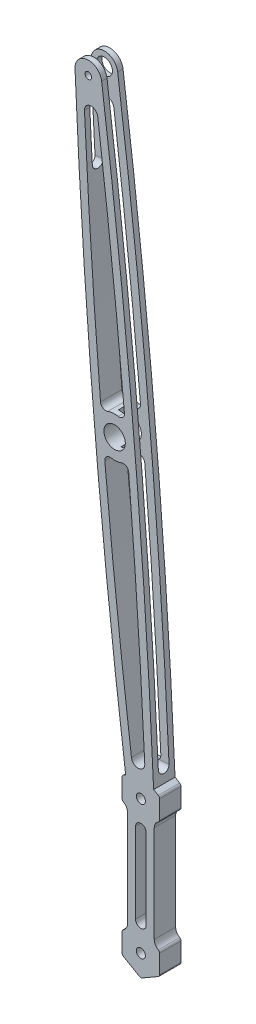
SolidWorks part; units mm, degrees
material "A2017"
ref_plane "正面" through (0, 0, 0) normal (0, 0, 1) x (1, 0, 0)
ref_plane "平面" through (0, 0, 0) normal (0, 1, 0) x (1, 0, 0)
ref_plane "右側面" through (0, 0, 0) normal (1, 0, 0) x (0, 0, -1)
sketch "ｽｹｯﾁ1" plane through (0, 0, 0) normal (0, 0, 1) x (1, 0, 0)
  line L0 (0, 0) -> (9.0749, 0) construction
  line L1 (0, 25) -> (0, 0) construction
  line L2 (0, -16.9171) -> (7, -20.9585)
  line L3 (7, 20.9585) -> (7, 29.0415)
  line L4 (7, 29.0415) -> (0, 33.0829)
  line L5 (0, 33.0829) -> (-7, 29.0415)
  line L6 (-7, 29.0415) -> (-7, 20.9585)
  line L7 (-7, 20.9585) -> (0, 16.9171)
  line L8 (0, 16.9171) -> (7, 20.9585)
  line L9 (-7, -20.9585) -> (0, -16.9171)
  line L10 (-7, -29.0415) -> (-7, -20.9585)
  line L11 (0, -33.0829) -> (-7, -29.0415)
  line L12 (7, -29.0415) -> (0, -33.0829)
  line L13 (7, -20.9585) -> (7, -29.0415)
  circle A0 centre (0, 25) radius 3
  circle A1 centre (0, -25) radius 3
  circle A2 centre (0, 25) radius 7 construction
  circle A3 centre (0, -25) radius 7 construction
  dimension "D1" = 6
  dimension "D2" = 50
  dimension "D3" = 14
extrude "ﾎﾞｽ - 押し出し1" add sketch "ｽｹｯﾁ1" along normal mid plane 8
sketch "ｽｹｯﾁ2" plane through (0, 0, 4) normal (0, 0, 1) x (1, 0, 0)
  line L0 (-7, 20.9585) -> (0, 16.9171) construction
  line L1 (5, -19.8038) -> (-5, -19.8038)
  line L2 (5, -19.8038) -> (5, 19.8038)
  line L3 (5, 19.8038) -> (-5, 19.8038)
  line L4 (-5, -19.8038) -> (-5, 19.8038)
  line L5 (5, -19.8038) -> (-5, 19.8038) construction
  line L6 (5, 19.8038) -> (-5, -19.8038) construction
  point P0 (0, 0)
  dimension "D1" = 10
extrude "ﾎﾞｽ - 押し出し2" add sketch "ｽｹｯﾁ2" against normal up to surface (8 mm away) up to face at (0, 25, -4)
fillet "ﾌｨﾚｯﾄ1" radius 3 4 edges at (5, -19.8038, 0) (-5, 19.8038, 0) (-5, -19.8038, 0) (5, 19.8038, 0)
fillet "ﾌｨﾚｯﾄ2" radius 1 10 edges at (-7, 20.9585, 0) (-7, 29.0415, 0) (0, 33.0829, 0) (7, 29.0415, 0) (7, 20.9585, 0) (7, -29.0415, 0) (0, -33.0829, 0) (-7, -29.0415, 0) (-7, -20.9585, 0) (7, -20.9585, 0)
sketch "ｽｹｯﾁ3" plane through (0, 0, -4) normal (0, 0, -1) x (-1, 0, 0)
  line L0 (0, -15) -> (0, 15) construction
  line L1 (-2, -15) -> (-2, 15)
  line L2 (2, -15) -> (2, 15)
  arc A0 (-2, -15) -> (2, -15) centre (0, -15) ccw
  arc A1 (2, 15) -> (-2, 15) centre (0, 15) ccw
  point P2 (0, 0)
  dimension "D1" = 4
  dimension "D2" = 30
extrude "ｶｯﾄ - 押し出し1" cut sketch "ｽｹｯﾁ3" against normal up to surface (8 mm away) up to face at (0, 0, 4)
sketch "ｽｹｯﾁ5" plane through (0, 0, 4) normal (0, 0, 1) x (1, 0, 0)
  circle A0 centre (0, -25) radius 3 construction
  circle A1 centre (0, 25) radius 3 construction
  circle A2 centre (0, -25) radius 3
  circle A3 centre (0, 25) radius 3
extrude "ﾎﾞｽ - 押し出し3" add sketch "ｽｹｯﾁ5" against normal blind 5
sketch "ｽｹｯﾁ8" [suppressed] plane through (0, 0, -4) normal (0, 0, -1) x (-1, 0, 0)
  circle A0 centre (0, -25) radius 3 construction
  circle A1 centre (0, 25) radius 3 construction
  circle A2 centre (0, -25) radius 3
  circle A3 centre (0, 25) radius 3
extrude "ﾎﾞｽ - 押し出し4" [suppressed] add sketch "ｽｹｯﾁ8" against normal blind 5
hole_wizard "M3 すきま穴1" positions "ｽｹｯﾁ6" profile "ｽｹｯﾁ7" hole size "M3" standard "JIS" end condition through all
sketch "ｽｹｯﾁ6" plane through (0, 0, 4) normal (0, 0, -1) x (-1, 0, 0)
  point P0 (0, 25)
  point P3 (0, -25)
sketch "ｽｹｯﾁ7" plane through (0, 25, 4) normal (1, 0, 0) x (0, -1, 0)
  line L0 (0, 0) -> (0, 8)
  line L1 (0, 8) -> (1.7, 8)
  line L2 (1.7, 8) -> (1.7, 0)
  line L5 (1.7, 0) -> (0, 0)
  line L11 (0, -6.35) -> (0, 107.95) construction
  dimension "通し穴の直径" = 3.4
  dimension "通し穴の深さ" = 8
sketch "ｽｹｯﾁ9" plane through (0, 0, 4) normal (0, 0, 1) x (1, 0, 0)
  line L0 (0, 25) -> (0, 298.9535) construction
  line L1 (0, 25) -> (-19.61, 249.1438) construction
  line L2 (0, 25) -> (-19.61, 249.1438) construction
  line L3 (-7.4715, 24.3463) -> (-27.0815, 248.4901) construction
  line L4 (7.4715, 25.6537) -> (-12.1386, 249.7975) construction
  line L15 (-7, 28.4641) -> (-7, 21.5359)
  line L16 (-5, 18.0718) -> (-5, -18.0718)
  line L17 (-7, -21.5359) -> (-7, -28.4641)
  line L18 (-6.5, -29.3301) -> (-0.5, -32.7942)
  line L19 (0.5, -32.7942) -> (6.5, -29.3301)
  line L20 (7, -28.4641) -> (7, -21.5359)
  line L21 (5, -18.0718) -> (5, 18.0718)
  line L22 (7, 21.5359) -> (7, 28.4641)
  line L23 (6.5, 29.3301) -> (0.5, 32.7942)
  line L24 (-0.5, 32.7942) -> (-6.5, 29.3301)
  line L25 (-7, 28.4641) -> (-7, 21.5359)
  line L26 (-5, 18.0718) -> (-5, -18.0718)
  line L27 (-7, -21.5359) -> (-7, -28.4641)
  line L28 (-6.5, -29.3301) -> (-0.5, -32.7942)
  line L29 (0.5, -32.7942) -> (6.5, -29.3301)
  line L30 (7, -28.4641) -> (7, -21.5359)
  line L31 (5, -18.0718) -> (5, 18.0718)
  line L32 (7, 21.5359) -> (7, 28.4641)
  line L33 (6.5, 29.3301) -> (0.5, 32.7942)
  line L34 (-0.5, 32.7942) -> (-6.5, 29.3301)
  arc A0 (-7.4715, 24.3463) -> (7.4715, 25.6537) centre (0, 25) ccw construction
  arc A1 (-12.1386, 249.7975) -> (-27.0815, 248.4901) centre (-19.61, 249.1438) ccw construction
  circle A2 centre (-19.61, 249.1438) radius 5 construction
  circle A3 centre (0, 25) radius 5
  arc A4 (-14.6533, 249.8004) -> (4.9954, 25.2141) centre (-2530.1776, -83.4321) cw
  arc A5 (-24.6055, 248.9297) -> (-4.9567, 24.3434) centre (2510.5676, 357.5759) ccw
  arc A6 (-14.6533, 249.8004) -> (-24.6055, 248.9297) centre (-19.61, 249.1438) ccw
  arc A16 (-7, 21.5359) -> (-6.5, 20.6699) centre (-6, 21.5359) ccw
  arc A17 (-5, 18.0718) -> (-6.5, 20.6699) centre (-8, 18.0718) ccw
  arc A18 (-6.5, -20.6699) -> (-5, -18.0718) centre (-8, -18.0718) ccw
  arc A19 (-6.5, -20.6699) -> (-7, -21.5359) centre (-6, -21.5359) ccw
  arc A20 (-7, -28.4641) -> (-6.5, -29.3301) centre (-6, -28.4641) ccw
  arc A21 (-0.5, -32.7942) -> (0.5, -32.7942) centre (0, -31.9282) ccw
  arc A22 (6.5, -29.3301) -> (7, -28.4641) centre (6, -28.4641) ccw
  arc A23 (7, -21.5359) -> (6.5, -20.6699) centre (6, -21.5359) ccw
  arc A24 (5, -18.0718) -> (6.5, -20.6699) centre (8, -18.0718) ccw
  arc A25 (6.5, 20.6699) -> (5, 18.0718) centre (8, 18.0718) ccw
  arc A26 (6.5, 20.6699) -> (7, 21.5359) centre (6, 21.5359) ccw
  arc A27 (7, 28.4641) -> (6.5, 29.3301) centre (6, 28.4641) ccw
  arc A28 (0.5, 32.7942) -> (-0.5, 32.7942) centre (0, 31.9282) ccw
  arc A29 (-6.5, 29.3301) -> (-7, 28.4641) centre (-6, 28.4641) ccw
  arc A30 (-7, 21.5359) -> (-6.5, 20.6699) centre (-6, 21.5359) ccw
  arc A31 (-5, 18.0718) -> (-6.5, 20.6699) centre (-8, 18.0718) ccw
  arc A32 (-6.5, -20.6699) -> (-5, -18.0718) centre (-8, -18.0718) ccw
  arc A33 (-6.5, -20.6699) -> (-7, -21.5359) centre (-6, -21.5359) ccw
  arc A34 (-7, -28.4641) -> (-6.5, -29.3301) centre (-6, -28.4641) ccw
  arc A35 (-0.5, -32.7942) -> (0.5, -32.7942) centre (0, -31.9282) ccw
  arc A36 (6.5, -29.3301) -> (7, -28.4641) centre (6, -28.4641) ccw
  arc A37 (7, -21.5359) -> (6.5, -20.6699) centre (6, -21.5359) ccw
  arc A38 (5, -18.0718) -> (6.5, -20.6699) centre (8, -18.0718) ccw
  arc A39 (6.5, 20.6699) -> (5, 18.0718) centre (8, 18.0718) ccw
  arc A40 (6.5, 20.6699) -> (7, 21.5359) centre (6, 21.5359) ccw
  arc A41 (7, 28.4641) -> (6.5, 29.3301) centre (6, 28.4641) ccw
  arc A42 (0.5, 32.7942) -> (-0.5, 32.7942) centre (0, 31.9282) ccw
  arc A43 (-6.5, 29.3301) -> (-7, 28.4641) centre (-6, 28.4641) ccw
  point P4 (-9.805, 137.0719)
  arc M28 (0.5, 32.7942) -> (-0.5, 32.7942) centre (0, 31.9282) ccw
  line M29 (-0.5, 32.7942) -> (-6.5, 29.3301)
  dimension "D5" = 10
  dimension "D1" = 5
  dimension "D2" = 225
  dimension "D4" = 15
  dimension "D3" = 0
extrude "ﾎﾞｽ - 押し出し5" add sketch "ｽｹｯﾁ9" against normal up to surface (8 mm away) contours A4 A6 A5 L33 M29 M28 region at (-10.1534, 141.0541, 4) up to face at (0, 0, -4)
sketch "ｽｹｯﾁ12" plane through (0, 0, -4) normal (0, 0, -1) x (-1, 0, 0)
  line L0 (19.61, 249.1438) -> (0, 25) construction
hole_wizard "M3 ねじ穴1" positions "ｽｹｯﾁ19" profile "ｽｹｯﾁ20" tap size "M3" standard "JIS" end condition through all
sketch "ｽｹｯﾁ19" plane through (0, 0, 4) normal (0, 0, 1) x (1, 0, 0)
  point P0 (-19.61, 249.1438)
sketch "ｽｹｯﾁ20" plane through (-19.61, 249.1438, 4) normal (1, 0, 0) x (0, -1, 0)
  line L0 (0, 0) -> (0, 8)
  line L1 (0, 8) -> (1.25, 8)
  line L2 (1.25, 8) -> (1.25, 0)
  line L5 (1.25, 0) -> (0, 0)
  line L11 (0, -6.35) -> (0, 107.95) construction
  dimension "次ｻｰﾌｪｽまでのねじ下穴ﾄﾞﾘﾙ直径" = 2.5
  dimension "次ｻｰﾌｪｽまでのねじ下穴ﾄﾞﾘﾙの深さ" = 8
cosmetic thread "穴のねじ山1" parameters "D2"=3
sketch "ｽｹｯﾁ10" plane through (0, 0, 4) normal (0, 0, 1) x (1, 0, 0)
  circle A0 centre (-19.61, 249.1438) radius 3
  dimension "D1" = 6
extrude "ｶｯﾄ - 押し出し2" [suppressed] cut sketch "ｽｹｯﾁ10" against normal blind 6
sketch "ｽｹｯﾁ21" plane through (0, 0, -4) normal (0, 0, -1) x (-1, 0, 0)
  circle A0 centre (19.61, 249.1438) radius 3
  dimension "D1" = 6
extrude "ｶｯﾄ - 押し出し8" cut sketch "ｽｹｯﾁ21" against normal blind 6
ref_plane "平面1" through (2.1706, 0.1899, 0) normal (0.9962, 0.0872, 0) x (0.0872, -0.9962, 0)
sketch "ｽｹｯﾁ13" plane through (0, 0, -4) normal (0, 0, -1) x (-1, 0, 0)
  line L0 (19.61, 249.1438) -> (0, 25) construction
  arc A2 (17.6274, 249.4065) -> (-1.7741, 30.1938) centre (2530.1776, -83.4321) ccw
  arc A3 (17.6274, 249.4065) -> (-1.7741, 30.1938) centre (2530.1776, -83.4321) ccw
  arc A4 (21.0716, 237.1884) -> (16.0946, 237.6238) centre (18.5745, 237.3071) ccw
  arc A5 (2.6995, 30.1943) -> (21.6082, 249.0582) centre (-2510.5676, 357.5759) ccw
  arc A6 (2.6995, 30.1943) -> (21.6082, 249.0582) centre (-2510.5676, 357.5759) ccw
  arc A7 (-1.4616, 36.9554) -> (3.5154, 36.52) centre (1.0356, 36.8367) ccw
  dimension "D3" = 5
  dimension "D1" = 3
  dimension "D2" = 3
extrude "ｶｯﾄ - 押し出し3" cut sketch "ｽｹｯﾁ13" against normal through all contours A3 A7 A6 A4 region at (-9.805, 137.0719, -4)
sketch "ｽｹｯﾁ14" plane through (0, 0, -4) normal (0, 0, -1) x (-1, 0, 0)
  line L0 (14.2879, 136.6797) -> (5.3221, 137.4641) construction
  arc A0 (3.5154, 36.52) -> (21.0716, 237.1884) centre (-2510.5676, 357.5759) ccw construction
  arc A1 (16.0946, 237.6238) -> (-1.4616, 36.9554) centre (2530.1776, -83.4321) ccw construction
  circle A2 centre (9.805, 137.0719) radius 7.5
  arc A3 (5.6744, 29.8068) -> (24.6055, 248.9297) centre (-2510.5676, 357.5759) ccw construction
extrude "ﾎﾞｽ - 押し出し6" add sketch "ｽｹｯﾁ14" against normal up to surface (8 mm away) up to face at (-9.805, 137.0719, 4)
fillet "ﾌｨﾚｯﾄ3" radius 2 4 edges at (-4.8058, 131.481, 0) (-13.7574, 130.6978, 0) (-14.8042, 142.6628, 0) (-5.8526, 143.446, 0)
sketch "ｽｹｯﾁ15" plane through (0, 0, 4) normal (0, 0, 1) x (1, 0, 0)
  line L0 (-19.61, 249.1438) -> (0, 25) construction
  circle A0 centre (-9.805, 137.0719) radius 4
  dimension "D1" = 8
extrude "ｶｯﾄ - 押し出し4" cut sketch "ｽｹｯﾁ15" against normal through all
sketch "ｽｹｯﾁ16" plane through (2.1706, 0.1899, 0) normal (0.9962, 0.0872, 0) x (0.0872, -0.9962, 0)
  line L0 (-254.9049, 0) -> (-34.9049, 0) construction
  line L1 (-254.9049, 4) -> (-254.9049, -4) construction
  line L2 (-254.9049, 2) -> (-34.9049, 2)
  line L3 (-254.9049, -2) -> (-34.9049, -2)
  arc A0 (-254.9049, 2) -> (-254.9049, -2) centre (-254.9049, 0) ccw
  arc A1 (-34.9049, -2) -> (-34.9049, 2) centre (-34.9049, 0) ccw
  point P5 (-144.9049, 0)
  dimension "D1" = 4
  dimension "D2" = 220
extrude "ｶｯﾄ - 押し出し6" cut sketch "ｽｹｯﾁ16" along normal through all
sketch "ｽｹｯﾁ22" plane through (2.1706, 0.1899, 0) normal (0.9962, 0.0872, 0) x (0, 0, -1)
  line L0 (0, 254.9049) -> (0, 219.9049) construction
  line L1 (-2, 254.9049) -> (2, 254.9049) construction
  line L2 (2, 254.9049) -> (2, 219.9049)
  line L3 (-2, 254.9049) -> (-2, 219.9049)
  line L4 (2, 252.9049) -> (2, 254.9049) construction
  arc A0 (2, 254.9049) -> (-2, 254.9049) centre (0, 254.9049) ccw
  arc A1 (-2, 219.9049) -> (2, 219.9049) centre (0, 219.9049) ccw
  point P5 (0, 237.4049)
  dimension "D1" = 35
extrude "ｶｯﾄ - 押し出し9" cut sketch "ｽｹｯﾁ22" against normal through all
